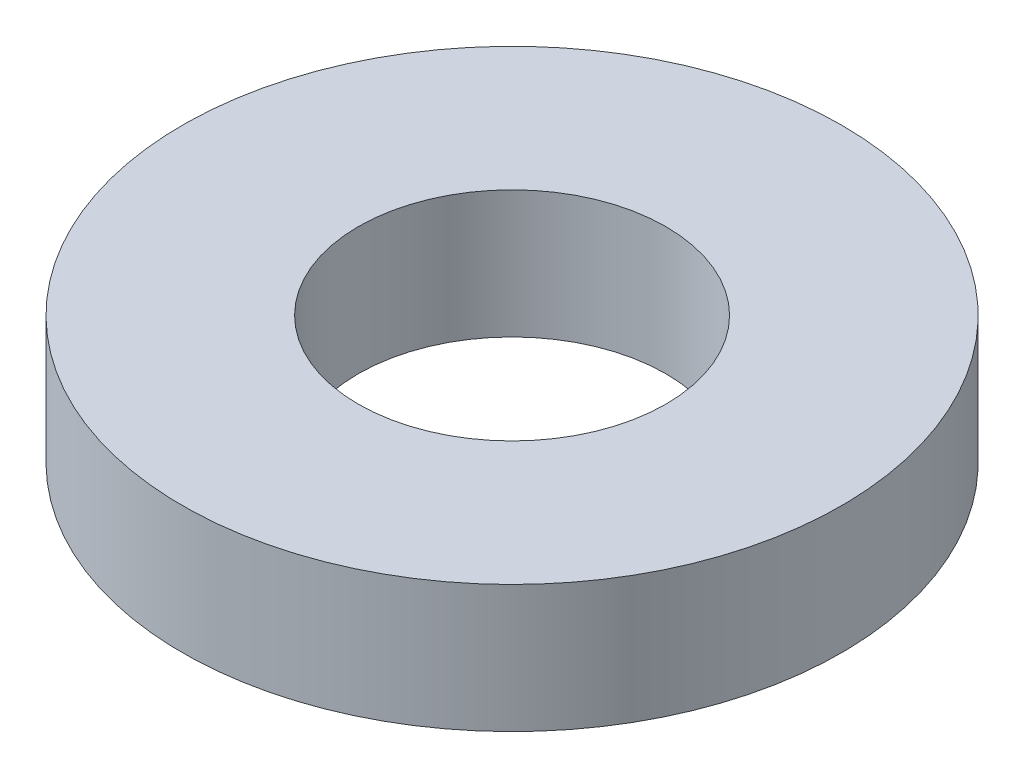
SolidWorks part; units mm, degrees
ref_plane "Front Plane" through (0, 0, 0) normal (0, 0, 1) x (1, 0, 0)
ref_plane "Top Plane" through (0, 0, 0) normal (0, 1, 0) x (1, 0, 0)
ref_plane "Right Plane" through (0, 0, 0) normal (1, 0, 0) x (0, 0, -1)
sketch "Sketch1" plane through (0, 0, 0) normal (0, 1, 0) x (1, 0, 0)
  circle A0 centre (0, 0) radius 75
  dimension "FLANGE_OD" = 150
extrude "Boss-Extrude1" add sketch "Sketch1" along normal blind 29
sketch "Sketch2" plane through (0, 0, 0) normal (0, 1, 0) x (1, 0, 0)
  circle A0 centre (0, 0) radius 35
  dimension "BORE_D" = 70
extrude "Cut-Extrude1" cut sketch "Sketch2" along normal through all
sketch "Sketch3" plane through (0, 29, 0) normal (0, 1, 0) x (1, 0, 0)
  circle A0 centre (0, 0) radius 22.854 construction
  circle A1 centre (-22.854, 0) radius 7.0733
  dimension "BOLT_D" = 14.1465
  dimension "BOLT_PCD" = 45.7081
extrude "Cut-Extrude2" cut sketch "Sketch3" against normal blind 23.9975 rebuild error yes
pattern_circular "CirPattern1" count 8 over 360 rebuild error yes
